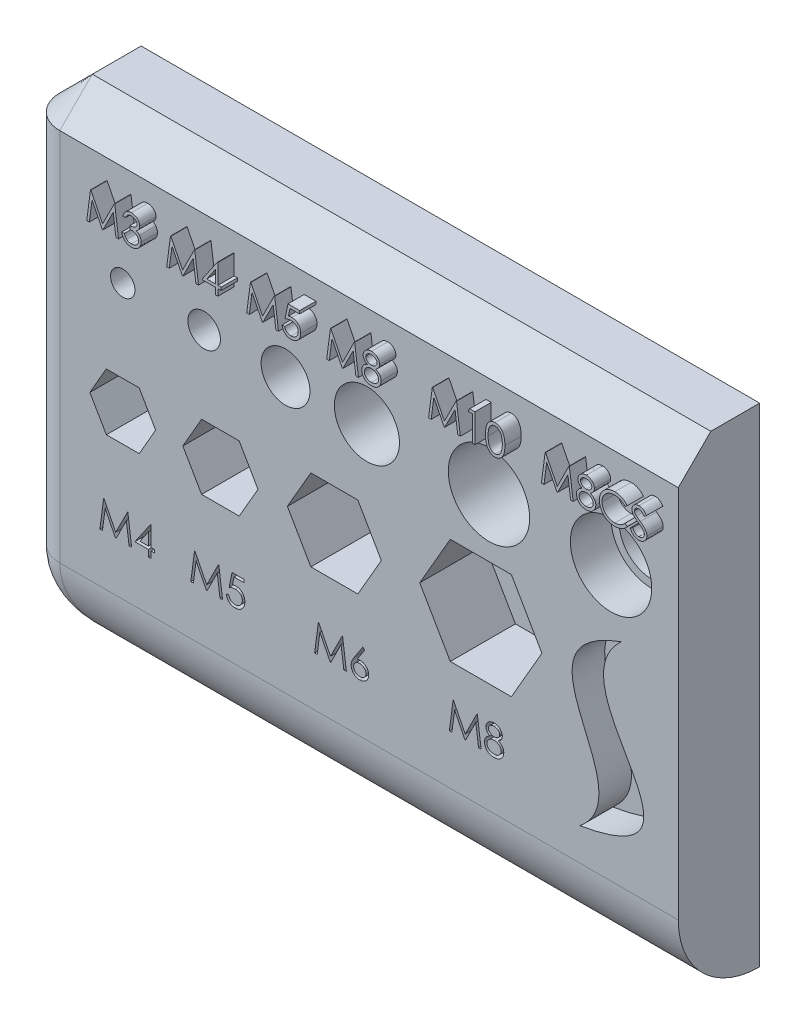
SolidWorks part; units mm, degrees
ref_plane "Front Plane" through (0, 0, 0) normal (0, 0, 1) x (1, 0, 0)
ref_plane "Top Plane" through (0, 0, 0) normal (0, 1, 0) x (1, 0, 0)
ref_plane "Right Plane" through (0, 0, 0) normal (1, 0, 0) x (0, 0, -1)
sketch "Sketch1" plane through (0, 0, 0) normal (0, 0, 1) x (1, 0, 0)
  line L1 (-50, -30) -> (50, -30)
  line L2 (-50, -30) -> (-50, 30)
  line L3 (-50, 30) -> (50, 30)
  line L4 (50, -30) -> (50, 30)
  line L5 (-50, -30) -> (50, 30) construction
  line L6 (-50, 30) -> (50, -30) construction
  point P0 (0, 0)
  dimension "D1" = 100
  dimension "D2" = 60
extrude "Boss-Extrude1" add sketch "Sketch1" along normal blind 10
fillet "Fillet2" radius 4 1 edges at (-50, 0, 10)
chamfer "Chamfer1" distance 4 angle 45 3 edges at (-50, 30, 3) (-48.8284, 30, 8.8284) (2, 30, 10)
fillet "Fillet3" radius 10 3 edges at (-50, -30, 3) (-48.8284, -30, 8.8284) (2, -30, 10)
sketch "Sketch2" plane through (0, 0, 10) normal (0, 0, 1) x (1, 0, 0)
  line L0 (-46, 13.6417) -> (50, 13.6417) construction
  line L1 (-46, 26) -> (-46, -20) construction
  line L2 (50, -20) -> (50, 26) construction
  circle A0 centre (-38.2587, 13.6417) radius 1.5
  circle A1 centre (-28.2587, 13.6417) radius 2
  circle A2 centre (-18.2587, 13.6417) radius 3
  circle A3 centre (-8.2587, 13.6417) radius 4
  circle A4 centre (6.7413, 13.6417) radius 5
  circle A5 centre (21.7413, 13.6417) radius 4
  point P18 (-46, 11.584)
  point P19 (-46, 13.6417)
  point P20 (-21.5124, 16.0807)
  dimension "D1" = 3
  dimension "D2" = 4
  dimension "D3" = 6
  dimension "D4" = 8
  dimension "D5" = 10
  dimension "D6" = 8
  dimension "D7" = 20
  dimension "D8" = 10
  dimension "D9" = 10
  dimension "D10" = 15
  dimension "D11" = 15
extrude "Cut-Extrude1" cut sketch "Sketch2" against normal blind 10
sketch "Sketch3" plane through (0, 0, 10) normal (0, 0, 1) x (1, 0, 0)
  circle A0 centre (21.7413, 13.6417) radius 5
  dimension "D1" = 10
extrude "Cut-Extrude2" cut sketch "Sketch3" against normal blind 5
sketch "Sketch4" plane through (0, 0, 10) normal (0, 0, 1) x (1, 0, 0)
  line L0 (-46, 0) -> (37.7227, 0) construction
  line L1 (-46, 26) -> (-46, -20) construction
  line L2 (-38.2587, 13.6417) -> (-38.2587, -8.9635) construction
  line L3 (-34.2173, 0.0094) -> (-36.2462, 3.5047)
  line L4 (-36.2462, 3.5047) -> (-40.2876, 3.4953)
  line L5 (-40.2876, 3.4953) -> (-42.3002, -0.0094)
  line L6 (-42.3002, -0.0094) -> (-40.2713, -3.5047)
  line L7 (-40.2713, -3.5047) -> (-36.2299, -3.4953)
  line L8 (-36.2299, -3.4953) -> (-34.2173, 0.0094)
  line L10 (-30.8776, 0) -> (-28.5682, -4)
  line L11 (-28.5682, -4) -> (-23.9493, -4)
  line L12 (-23.9493, -4) -> (-21.6399, 0)
  line L13 (-21.6399, 0) -> (-23.9493, 4)
  line L14 (-23.9493, 4) -> (-28.5682, 4)
  line L15 (-28.5682, 4) -> (-30.8776, 0)
  line L16 (-18.0323, 0) -> (-15.1455, -5)
  line L17 (-15.1455, -5) -> (-9.372, -5)
  line L18 (-9.372, -5) -> (-6.4852, 0)
  line L19 (-6.4852, 0) -> (-9.372, 5)
  line L20 (-9.372, 5) -> (-15.1455, 5)
  line L21 (-15.1455, 5) -> (-18.0323, 0)
  line L22 (-1.7643, 0) -> (1.9885, -6.5)
  line L23 (1.9885, -6.5) -> (9.494, -6.5)
  line L24 (9.494, -6.5) -> (13.2468, 0)
  line L25 (13.2468, 0) -> (9.494, 6.5)
  line L26 (9.494, 6.5) -> (1.9885, 6.5)
  line L27 (1.9885, 6.5) -> (-1.7643, 0)
  circle A0 centre (-38.2587, 0) radius 3.5 construction
  circle A1 centre (-26.2587, 0) radius 4 construction
  circle A2 centre (-12.2587, 0) radius 5 construction
  circle A3 centre (5.7413, 0) radius 6.5 construction
  point P14 (-38.2669, 3.5)
  point P34 (4.043, 0)
  point P42 (0, 0)
  point P43 (0, 0)
  point P44 (0, 0)
  point P45 (0, 0)
  dimension "D1" = 7
  dimension "D2" = 12
  dimension "D3" = 8
  dimension "D4" = 14
  dimension "D5" = 10
  dimension "D6" = 13
  dimension "D7" = 18
extrude "Cut-Extrude3" cut sketch "Sketch4" against normal blind 8
sketch "Sketch5" plane through (0, 0, 10) normal (0, 0, 1) x (1, 0, 0)
  line L0 (-46, 0) -> (46.1645, 0) construction
  line L1 (-46, 26) -> (-46, -20) construction
sketch "Sketch6" plane through (0, 0, 10) normal (0, 0, 1) x (1, 0, 0)
  line L0 (-30.8776, 0) -> (-21.6399, 0) construction
  line L1 (-21.6399, 0) -> (-23.9493, 4) construction
  line L2 (-23.9493, 4) -> (-28.5682, -4) construction
  line L3 (-1.7643, 0) -> (13.2468, 0) construction
  line L4 (13.2468, 0) -> (9.494, 6.5) construction
  line L5 (9.494, 6.5) -> (1.9885, -6.5) construction
  line L6 (-18.0323, 0) -> (-6.4852, 0) construction
  line L7 (-6.4852, 0) -> (-9.372, 5) construction
  line L8 (-9.372, 5) -> (-15.1455, -5) construction
  line L9 (-42.3002, -0.0094) -> (-34.2173, 0.0094) construction
  line L10 (-34.2173, 0.0094) -> (-36.2462, 3.5047) construction
  line L11 (-36.2462, 3.5047) -> (-40.2713, -3.5047) construction
  circle A0 centre (-26.2587, 0) radius 2.5
  circle A1 centre (5.7413, 0) radius 4
  circle A2 centre (-38.2587, 0) radius 2
  circle A3 centre (-12.2587, 0) radius 3
  dimension "D1" = 5
  dimension "D2" = 8
  dimension "D3" = 4
  dimension "D4" = 6
extrude "Cut-Extrude4" cut sketch "Sketch6" against normal blind 45
sketch "Sketch7" plane through (50, 0, 0) normal (1, 0, 0) x (0, 0, -1)
  line L1 (-58.1523, -132.8342) -> (12.8003, -132.8342)
  line L2 (-58.1523, -132.8342) -> (-58.1523, 39.7633)
  line L3 (-58.1523, 39.7633) -> (12.8003, 39.7633)
  line L4 (12.8003, -132.8342) -> (12.8003, 39.7633)
  line L5 (-58.1523, -132.8342) -> (12.8003, 39.7633) construction
  line L6 (-58.1523, 39.7633) -> (12.8003, -132.8342) construction
  point P0 (-22.676, -46.5355)
extrude "Cut-Extrude5" cut sketch "Sketch7" against normal blind 20
sketch "Sketch9" plane through (0, 0, 10) normal (0, 0, 1) x (1, 0, 0)
  line L0 (-40.9525, 20.0807) -> (27.5575, 20.0807) construction
  line L1 (-40.9525, -12.8954) -> (24.7693, -12.8954) construction
  text T0 "M3  M4  M5  M8    M10   M8CS"
extrude "Boss-Extrude3" add sketch "Sketch9" along normal blind 2
sketch "Sketch10" plane through (0, 0, 10) normal (0, 0, 1) x (1, 0, 0)
  line L0 (-41.3388, -13.9381) -> (32.9571, -13.9381) construction
  text T0 "M4   M5      M6       M8"
extrude "Cut-Extrude6" cut sketch "Sketch10" against normal blind 2
sketch "Sketch11" plane through (0, 0, 10) normal (0, 0, 1) x (1, 0, 0)
  spline S0 degree 3 poles (22.9967, 6.1038) (8.2129, 0.7562) (26.3295, -9.0988) (17.8972, -16.0202) knots 0 0 0 0 1 1 1 1
  spline S1 degree 3 poles (22.9967, 6.1038) (14.0015, -2.2741) (37.0545, -12.7072) (17.8972, -16.0202) knots 0 0 0 0 1 1 1 1
extrude "Cut-Extrude7" cut sketch "Sketch11" against normal blind 4
